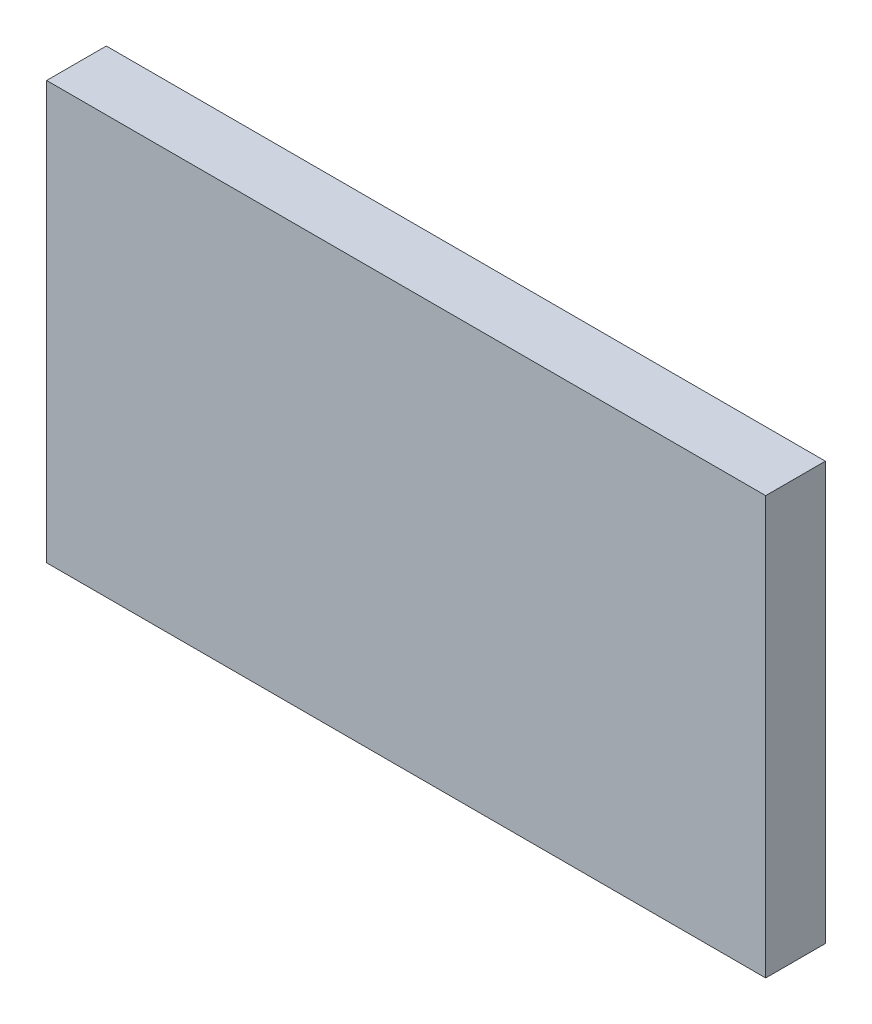
SolidWorks part; units mm, degrees
material "Polyurethane Foam Rigid"
ref_plane "X-Y Datum" through (0, 0, 0) normal (0, 0, 1) x (1, 0, 0)
ref_plane "X-Z Datum" through (0, 0, 0) normal (0, 1, 0) x (1, 0, 0)
ref_plane "Y-Z Datum" through (0, 0, 0) normal (1, 0, 0) x (0, 0, -1)
sketch "Sketch1" plane through (0, 0, 0) normal (0, 0, 1) x (1, 0, 0)
  line L1 (-153.0248, -88.9) -> (153.0248, -88.9)
  line L2 (-153.0248, -88.9) -> (-153.0248, 88.9)
  line L3 (-153.0248, 88.9) -> (153.0248, 88.9)
  line L4 (153.0248, -88.9) -> (153.0248, 88.9)
  line L5 (-153.0248, -88.9) -> (153.0248, 88.9) construction
  line L6 (-153.0248, 88.9) -> (153.0248, -88.9) construction
  point P0 (0, 0)
  dimension "D1" = 306.0497
  dimension "D2" = 177.8
extrude "Boss-Extrude1" add sketch "Sketch1" against normal blind 25.4
